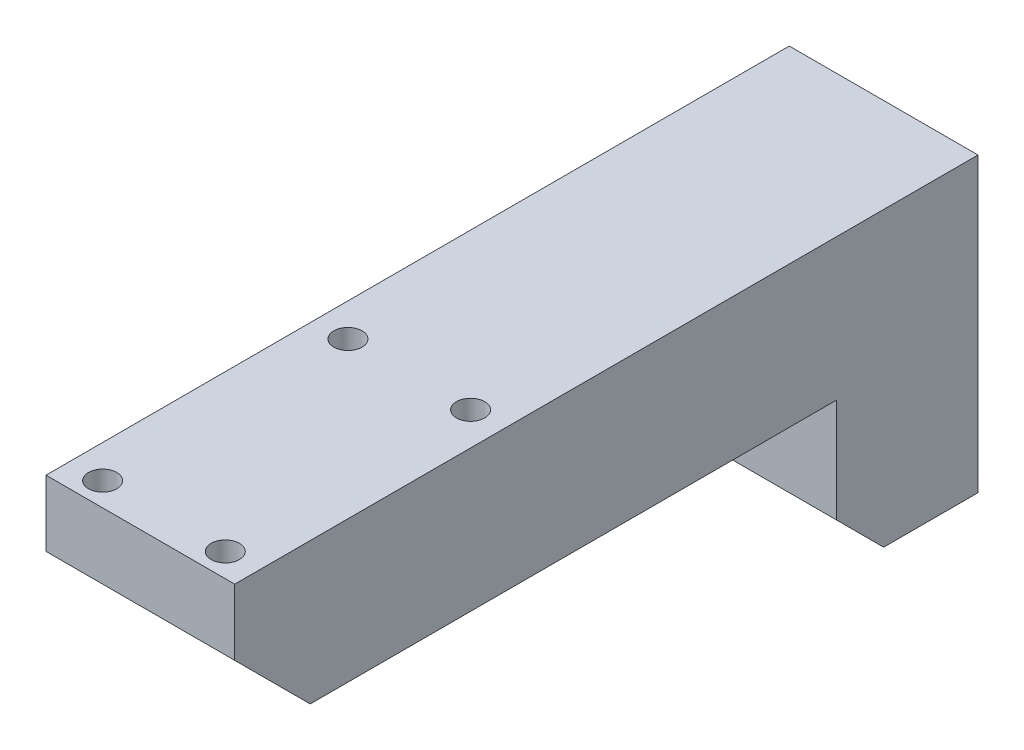
SolidWorks part; units mm, degrees
ref_plane "Płaszczyzna przednia" through (0, 0, 0) normal (0, 0, 1) x (1, 0, 0)
ref_plane "Płaszczyzna górna" through (0, 0, 0) normal (0, 1, 0) x (1, 0, 0)
ref_plane "Płaszczyzna prawa" through (0, 0, 0) normal (1, 0, 0) x (0, 0, -1)
sketch "Szkic1" plane through (0, 0, 0) normal (0, 1, 0) x (1, 0, 0)
  line L1 (20, -78.775) -> (-20, -78.775)
  line L2 (20, -78.775) -> (20, 78.775)
  line L3 (20, 78.775) -> (-20, 78.775)
  line L4 (-20, -78.775) -> (-20, 78.775)
  line L5 (20, -78.775) -> (-20, 78.775) construction
  line L6 (20, 78.775) -> (-20, -78.775) construction
  point P0 (0, 0)
  dimension "D1" = 40
  dimension "D2" = 157.55
extrude "Dodanie-wyciągnięcie1" add sketch "Szkic1" along normal blind 30
sketch "Szkic2" plane through (0, 0, 0) normal (0, -1, 0) x (-1, 0, 0)
  line L0 (20, 78.775) -> (20, -78.775) construction
  line L1 (-20, 78.775) -> (20, 78.775)
  line L2 (-20, 78.775) -> (-20, 48.775)
  line L3 (-20, 48.775) -> (20, 48.775)
  line L4 (20, 78.775) -> (20, 48.775)
  dimension "D1" = 30
extrude "Dodanie-wyciągnięcie2" add sketch "Szkic2" along normal blind 32
sketch "Szkic3" plane through (0, 30, 0) normal (0, 1, 0) x (1, 0, 0)
  line L0 (-20, -78.775) -> (20, -78.775) construction
  line L1 (-20, 78.775) -> (-20, -78.775) construction
  line L2 (20, -78.775) -> (20, 78.775) construction
  circle A0 centre (-13, -73.775) radius 3
  circle A1 centre (13, -73.775) radius 3
  circle A2 centre (13, -21.775) radius 3
  circle A3 centre (-13, -21.775) radius 3
  dimension "D1" = 6
  dimension "D2" = 5
  dimension "D3" = 7
  dimension "D4" = 7
  dimension "D5" = 52
extrude "Wytnij-wyciągnięcie1" cut sketch "Szkic3" against normal blind 30
sketch "Szkic4" plane through (0, 0, 0) normal (0, -1, 0) x (1, 0, 0)
  circle A0 centre (13, 73.775) radius 5.5
  circle A1 centre (-13, 73.775) radius 5.5
  dimension "D1" = 11
chamfer "Sfazowanie1" distance 16 angle 45 1 edges at (0, 0, 78.775)
extrude "Wytnij-wyciągnięcie7" cut sketch "Szkic4" against normal blind 15
chamfer "Sfazowanie2" distance 10 angle 45 1 edges at (0, -32, -48.775)
hole_wizard "Otwór gwintowany M8x1.01" positions "Szkic5" profile "Szkic7" tap size "M8x1.0" standard "Ansi Metric"
sketch "Szkic5" plane through (0, 0, -78.775) normal (0, 0, -1) x (-1, 0, 0)
  line L1 (-13, -25) -> (13, -25)
  line L2 (-13, -25) -> (-13, 23)
  line L3 (-13, 23) -> (13, 23)
  line L4 (13, -25) -> (13, 23)
  line L5 (20, -32) -> (-20, -32) construction
  line L7 (20, 30) -> (20, -32) construction
  point P0 (-13, -25)
  point P2 (-13, 23)
  point P4 (13, 23)
  point P6 (13, -25)
  point P90 (0, 0)
  point P91 (0, 0)
  point P92 (0, 0)
  dimension "D1" = 48
  dimension "D2" = 26
  dimension "D3" = 7
  dimension "D4" = 7
sketch "Szkic7" plane through (13, -25, -78.775) normal (1, 0, 0) x (0, 1, 0)
  line L0 (0, 0) -> (0, 23.103)
  line L1 (0, 23.103) -> (3.5, 21)
  line L2 (3.5, 21) -> (3.5, 0)
  line L5 (3.5, 0) -> (0, 0)
  line L10 (0, 23.103) -> (-3.5, 21) construction
  line L11 (0, -6.35) -> (0, 107.95) construction
  dimension "Średnica wiertła gwintu" = 7
  dimension "Głębokość otworu gwintowanego" = 21
  dimension "Kąt wiertła" = 118
cosmetic thread "Gwint otworu1" parameters "D1"=16, "D2"=8
cosmetic thread "Gwint otworu2" parameters "D1"=16, "D2"=8
cosmetic thread "Gwint otworu3" parameters "D1"=16, "D2"=8
cosmetic thread "Gwint otworu4" parameters "D1"=16, "D2"=8
